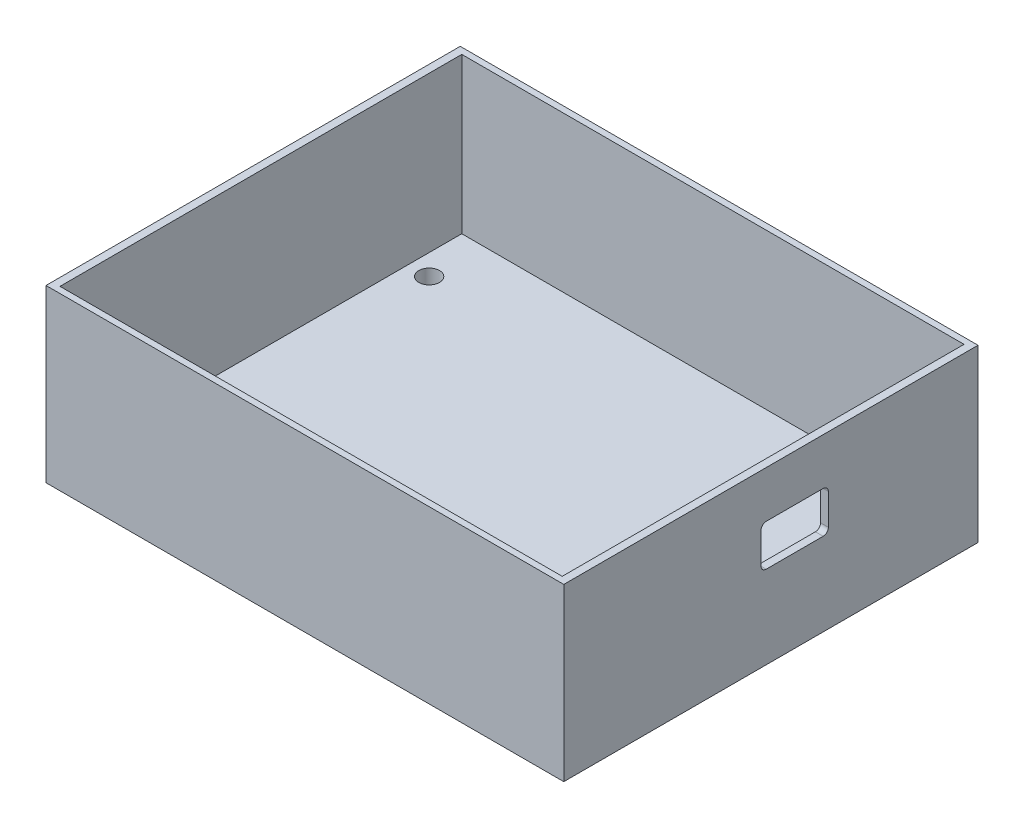
SolidWorks part; units mm, degrees
ref_plane "Front" through (0, 0, 0) normal (0, 0, 1) x (1, 0, 0)
ref_plane "Top" through (0, 0, 0) normal (0, 1, 0) x (1, 0, 0)
ref_plane "Right" through (0, 0, 0) normal (1, 0, 0) x (0, 0, -1)
sketch "Sketch1" plane through (0, 0, 0) normal (0, 1, 0) x (1, 0, 0)
  line L1 (-50, -40) -> (50, -40)
  line L2 (-50, -40) -> (-50, 40)
  line L3 (-50, 40) -> (50, 40)
  line L4 (50, -40) -> (50, 40)
  line L5 (-50, -40) -> (50, 40) construction
  line L6 (-50, 40) -> (50, -40) construction
  point P0 (0, 0)
  dimension "D1" = 100
  dimension "D2" = 80
extrude "Boss-Extrude1" add sketch "Sketch1" along normal blind 3
sketch "Sketch2" plane through (0, 3, 0) normal (0, 1, 0) x (1, 0, 0)
  line L1 (-50, -40) -> (50, -40)
  line L2 (-50, -40) -> (-50, 40)
  line L3 (-50, 40) -> (50, 40)
  line L4 (50, -40) -> (50, 40)
  line L5 (-50, -40) -> (50, 40) construction
  line L6 (-50, 40) -> (50, -40) construction
  line L7 (-48.5, -38.8) -> (48.5, -38.8)
  line L8 (-48.5, -38.8) -> (-48.5, 38.8)
  line L9 (-48.5, 38.8) -> (48.5, 38.8)
  line L10 (48.5, -38.8) -> (48.5, 38.8)
  line L11 (-48.5, -38.8) -> (48.5, 38.8) construction
  line L12 (-48.5, 38.8) -> (48.5, -38.8) construction
  point P0 (0, 0)
  point P7 (0, 0)
  dimension "D1" = 97
extrude "Boss-Extrude2" add sketch "Sketch2" along normal blind 30
sketch "Sketch3" plane through (0, 3, 0) normal (0, 1, 0) x (1, 0, 0)
  line L1 (50, 40) -> (-50, 40) construction
  line L2 (-50, 40) -> (-50, -40) construction
  line L5 (50, -40) -> (50, 40) construction
  line L6 (-50, -40) -> (50, -40) construction
  circle A0 centre (-44.5, 28.5) radius 2
  circle A1 centre (44.5, 28.5) radius 2
  circle A2 centre (-44.5, -28.5) radius 2
  circle A3 centre (44.5, -28.5) radius 2
  point P0 (0, 0)
  dimension "D5" = 4
  dimension "D3" = 4
  dimension "D4" = 4
  dimension "D6" = 4
  dimension "D1" = 11.5
  dimension "D2" = 5.5
  dimension "D7" = 11.5
  dimension "D8" = 5.5
  dimension "D9" = 5.5
  dimension "D10" = 11.5
  dimension "D11" = 5.5
  dimension "D12" = 11.5
extrude "Cut-Extrude1" cut sketch "Sketch3" against normal blind 40
sketch "Sketch4" plane through (0, 3, 0) normal (0, 1, 0) x (1, 0, 0)
  line L2 (47.5, -37.5) -> (-47.5, -37.5)
  line L3 (47.5, -37.5) -> (47.5, 37.5)
  line L4 (47.5, 37.5) -> (-47.5, 37.5)
  line L5 (-47.5, -37.5) -> (-47.5, 37.5)
  line L6 (47.5, -37.5) -> (-47.5, 37.5) construction
  line L8 (47.5, 37.5) -> (-47.5, -37.5) construction
  point P0 (0, 0)
  dimension "D1" = 95
  dimension "D2" = 75
extrude "Boss-Extrude3" add sketch "Sketch4" against normal blind 5
extrude "Cut-Extrude2" cut sketch "Sketch3<2>" against normal blind 12
sketch "Sketch3<2>" plane through (0, 3, 0) normal (0, 1, 0) x (1, 0, 0) same geometry as "Sketch3"
sketch "Sketch5" plane through (50, 0, 0) normal (1, 0, 0) x (0, 0, -1)
  line L0 (-1.9, 16) -> (11.1, 16)
  line L1 (-1.9, 16) -> (-1.9, 24)
  line L2 (-1.9, 24) -> (11.1, 24)
  line L3 (11.1, 16) -> (11.1, 24)
  line L4 (-1.9, 16) -> (11.1, 24) construction
  line L5 (-1.9, 24) -> (11.1, 16) construction
  line L6 (50, 0) -> (-50, 0) construction
  line L7 (40, 33) -> (40, 0) construction
  point P0 (4.6, 20)
  dimension "D1" = 8
  dimension "D2" = 13
  dimension "D3" = 20
  dimension "D4" = 35.4
extrude "Cut-Extrude3" cut sketch "Sketch5" against normal blind 10
fillet "Fillet1" radius 1 1 edges at (49.25, 24, -11.1) type face fillet first side face at (49.25, 20, -11.1) second side face at (49.25, 24, -4.6)
fillet "Fillet2" radius 1 1 edges at (49.25, 24, 1.9) type face fillet first side face at (49.25, 20, 1.9) second side face at (49.25, 24, -4.1)
fillet "Fillet3" radius 1 1 edges at (49.25, 16, 1.9) type face fillet first side face at (49.25, 16, -4.6) second side face at (49.25, 19.5, 1.9)
fillet "Fillet4" radius 1 1 edges at (49.25, 16, -11.1) type face fillet first side face at (49.25, 19.5, -11.1) second side face at (49.25, 16, -5.1)
